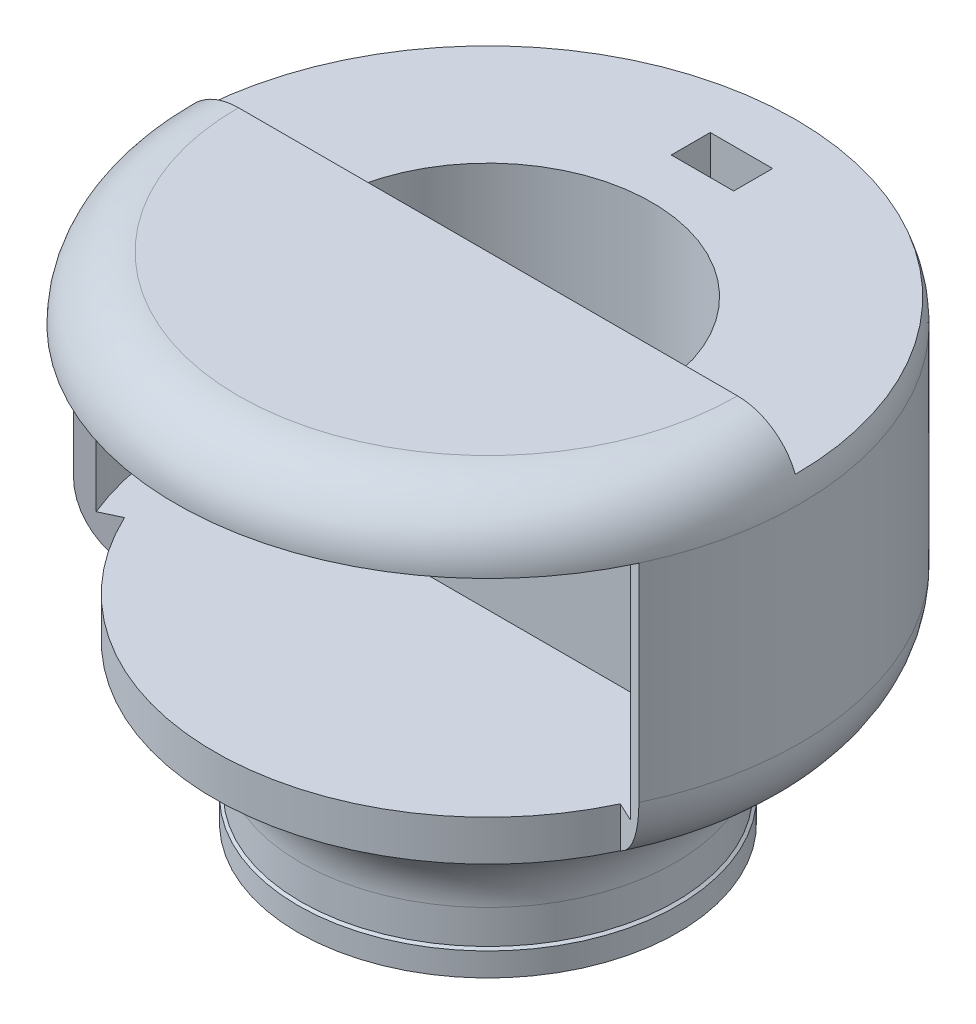
SolidWorks part; units mm, degrees
ref_plane "Front Plane" through (0, 0, 0) normal (0, 0, 1) x (1, 0, 0)
ref_plane "Top Plane" through (0, 0, 0) normal (0, 1, 0) x (1, 0, 0)
ref_plane "Right Plane" through (0, 0, 0) normal (1, 0, 0) x (0, 0, -1)
sketch "Sketch1" plane through (0, 0, 0) normal (0, 0, 1) x (1, 0, 0)
  line L0 (0, 0) -> (0, 90.2242) construction
  line L28 (0, 63.4279) -> (32, 63.4279)
  line L29 (40, 55.4279) -> (40, 28.8468)
  line L30 (22.5, 0) -> (24.35, 0)
  line L31 (24.35, 0) -> (24.35, 3)
  line L32 (24.35, 3) -> (24, 3.25)
  line L33 (24, 3.25) -> (24, 7.5811)
  line L34 (28.5399, 15.9588) -> (35.4601, 20.4691)
  line L35 (0, 13) -> (22, 13)
  line L36 (22.5, 12.5) -> (22.5, 0)
  line L37 (0, 13) -> (0, 63.4279)
  arc A0 (22, 13) -> (22.5, 12.5) centre (22, 12.5) cw
  arc A1 (24, 7.5811) -> (28.5399, 15.9588) centre (34, 7.5811) cw
  arc A2 (35.4601, 20.4691) -> (40, 28.8468) centre (30, 28.8468) ccw
  arc A3 (32, 63.4279) -> (40, 55.4279) centre (32, 55.4279) cw
  point P11 (22.9, 63.4279)
  point P18 (22.5, 13)
  point P21 (24, 13)
  point P24 (40, 23.4279)
  point P27 (40, 63.4279)
  point P28 (28.5604, 23.4279)
  point P31 (22.5, 17)
  dimension "D8" = 9.75
  dimension "D9" = 0.5
  dimension "D4" = 1.85
  dimension "D1" = 22.5
  dimension "D10" = 10
  dimension "D11" = 10
  dimension "D12" = 8
  dimension "D2" = 40
  dimension "D3" = 40
  dimension "D5" = 1.5
  dimension "D6" = 3
  dimension "D7" = 13
revolve "Revolve1" add sketch "Sketch1" angle 360 about L0
ref_plane "Plane1" through (0, 13, 0) normal (0, -1, 0) x (-1, 0, 0)
sketch "Sketch18" plane through (0, 0, 0) normal (0, 0, 1) x (1, 0, 0)
  line L0 (0, 0) -> (0, 101.5813) construction
  line L1 (-24.35, 0) -> (24.35, 0) construction
sketch "Sketch3" plane through (0, 0, 0) normal (0, 0, 1) x (1, 0, 0)
  point P0 (1.2404, 19.1989)
ref_point "Point1"
ref_plane "Plane2" through (0, 0, 22.9) normal (0, 0, 1) x (1, 0, 0)
ref_plane "Plane3" through (0, 0, 40) normal (0, 0, 1) x (1, 0, 0)
ref_plane "Plane4" through (0, 55.4279, 0) normal (0, 1, 0) x (1, 0, 0)
sketch "Sketch9" plane through (0, 55.4279, 0) normal (0, 1, 0) x (1, 0, 0)
  line L1 (-24, -1.7631) -> (24, -1.7631)
  arc A2 (-37, -1.6015) -> (37, -2.3985) centre (0, -2) ccw
  arc A3 (-37, -1.6015) -> (37, -2.3985) centre (0, -2) cw
  arc A6 (-24, -1.7631) -> (24, -1.7631) centre (0, -0.0603) cw
  dimension "D1" = 74
  dimension "D3" = 13
  dimension "D4" = 13
ref_plane "Plane5" through (0, 13, 0) normal (0, -1, 0) x (-1, 0, 0)
sketch "Sketch11" plane through (0, 13, 0) normal (0, -1, 0) x (-1, 0, 0)
  line L0 (-21, 0) -> (21, 0)
  arc A1 (-21, 0) -> (21, 0) centre (0, 0) cw
  dimension "D1" = 42
extrude "Cut-Extrude3" cut sketch "Sketch11" against normal blind 60
ref_plane "Plane6" through (0, 0, -40) normal (0, 0, -1) x (-1, 0, 0)
extrude "Cut-Extrude5" cut sketch "Sketch9" against normal blind 30 and the other way blind 2
sketch "Sketch19" plane through (0, 0, 0) normal (1, 0, 0) x (0, 0, -1)
  line L0 (-47.0647, 55.4279) -> (-35.0647, 55.4279)
  line L1 (31.2976, 55.4279) -> (-31.2976, 55.4279) construction
  line L2 (-35.0647, 55.4279) -> (-35.0647, 18.9279)
  line L3 (-35.0647, 18.9279) -> (-47.0647, 18.9279)
  line L4 (-47.0647, 18.9279) -> (-47.0647, 55.4279)
  dimension "D1" = 12
  dimension "D2" = 36.5
revolve "Cut-Revolve2" cut sketch "Sketch19" angle 65 about L0 other way angle 65
ref_plane "Plane7" through (0, 0, 22.5) normal (0, 0, -1) x (-1, 0, 0)
sketch "Sketch21" plane through (0, 0, 22.5) normal (0, 0, -1) x (-1, 0, 0)
  line L0 (0, 0) -> (0, 101.5813) construction
  line L1 (-1.625, 4) -> (1.625, 4)
  line L2 (-1.625, 4) -> (-1.625, 0)
  line L3 (-1.625, 0) -> (1.625, 0)
  line L4 (1.625, 4) -> (1.625, 0)
  line L5 (-1.625, 4) -> (1.625, 0) construction
  line L6 (-1.625, 0) -> (1.625, 4) construction
  line L7 (-22.5, 0) -> (22.5, 0) construction
  point P0 (0, 2)
  dimension "D1" = 4
  dimension "D2" = 3.25
extrude "Boss-Extrude3" add sketch "Sketch21" along normal blind 1.35
pattern_circular "CirPattern1" count 5 over 360 about axis through (0, 0, 0) along (0, -1, 0) of "Boss-Extrude3"
ref_plane "Plane8" through (0, 20.4691, 0) normal (0, 1, 0) x (1, 0, 0)
sketch "Sketch22" plane through (0, 63.4279, 0) normal (0, 1, 0) x (1, 0, 0)
  line L0 (-40, 0) -> (40, 0)
  arc A0 (-40, 0) -> (40, 0) centre (0, 0) cw
  arc A1 (36.2523, -16.9047) -> (-36.2523, -16.9047) centre (0, 0) ccw construction
extrude "Cut-Extrude9" cut sketch "Sketch22" against normal blind 5
sketch "Sketch23" plane through (0, 0, -40) normal (0, 0, -1) x (-1, 0, 0)
  line L0 (0, 0) -> (0, 101.5813) construction
  line L1 (44, 55.4279) -> (-44, 55.4279) construction
  circle A0 centre (0, 42.1379) radius 10
  dimension "D1" = 20
  dimension "D2" = 13.29
extrude "Cut-Extrude10" cut sketch "Sketch23" against normal blind 10
fillet "Fillet1" radius 5 1 edges at (1.8994, 32.3199, -34.9534)
sketch "Sketch24" plane through (0, 58.4279, 0) normal (0, 1, 0) x (1, 0, 0)
  line L1 (-7.5, 34) -> (7.5, 34)
  line L2 (-7.5, 34) -> (-7.5, 26)
  line L3 (-7.5, 26) -> (7.5, 26)
  line L4 (7.5, 34) -> (7.5, 26)
  line L5 (-7.5, 34) -> (7.5, 26) construction
  line L6 (-7.5, 26) -> (7.5, 34) construction
  arc A0 (39.4162, 0) -> (-39.4162, 0) centre (0, 0) ccw construction
  point P0 (0, 30)
  dimension "D1" = 30
  dimension "D2" = 8
  dimension "D3" = 15
extrude "Boss-Extrude4" add sketch "Sketch24" against normal blind 8
sketch "Sketch26" plane through (0, 58.4279, 0) normal (0, 1, 0) x (1, 0, 0)
  line L1 (-4, 32.5) -> (4, 32.5)
  line L2 (-4, 32.5) -> (-4, 27.5)
  line L3 (-4, 27.5) -> (4, 27.5)
  line L4 (4, 32.5) -> (4, 27.5)
  line L5 (-4, 32.5) -> (4, 27.5) construction
  line L6 (-4, 27.5) -> (4, 32.5) construction
  arc A0 (39.4162, 0) -> (-39.4162, 0) centre (0, 0) ccw construction
  point P0 (0, 30)
  dimension "D1" = 30
  dimension "D2" = 5
  dimension "D3" = 8
extrude "Cut-Extrude11" cut sketch "Sketch26" against normal blind 10
sketch "Sketch27" plane through (7.5, 0, 0) normal (1, 0, 0) x (0, 0, -1)
  line L0 (34, 50.4279) -> (34, 57.4279) construction
  line L1 (28, 56.4279) -> (32, 56.4279)
  line L2 (28, 56.4279) -> (28, 51.4279)
  line L3 (28, 51.4279) -> (32, 51.4279)
  line L4 (32, 56.4279) -> (32, 51.4279)
  line L5 (28, 56.4279) -> (32, 51.4279) construction
  line L6 (28, 51.4279) -> (32, 56.4279) construction
  line L7 (26, 50.4279) -> (26, 57.4279) construction
  line L8 (26, 50.4279) -> (34, 50.4279) construction
  point P0 (30, 53.9279)
  dimension "D1" = 8
  dimension "D2" = 3.5
  dimension "D3" = 5
  dimension "D4" = 4
extrude "Cut-Extrude12" cut sketch "Sketch27" against normal blind 5
ref_plane "Plane9" through (-39.4162, 58.4279, 0) normal (0.375, 0.927, 0) x (0.927, -0.375, 0)
ref_plane "Plane10" through (0, 58.4279, 0) normal (0, 1, 0) x (1, 0, 0)
